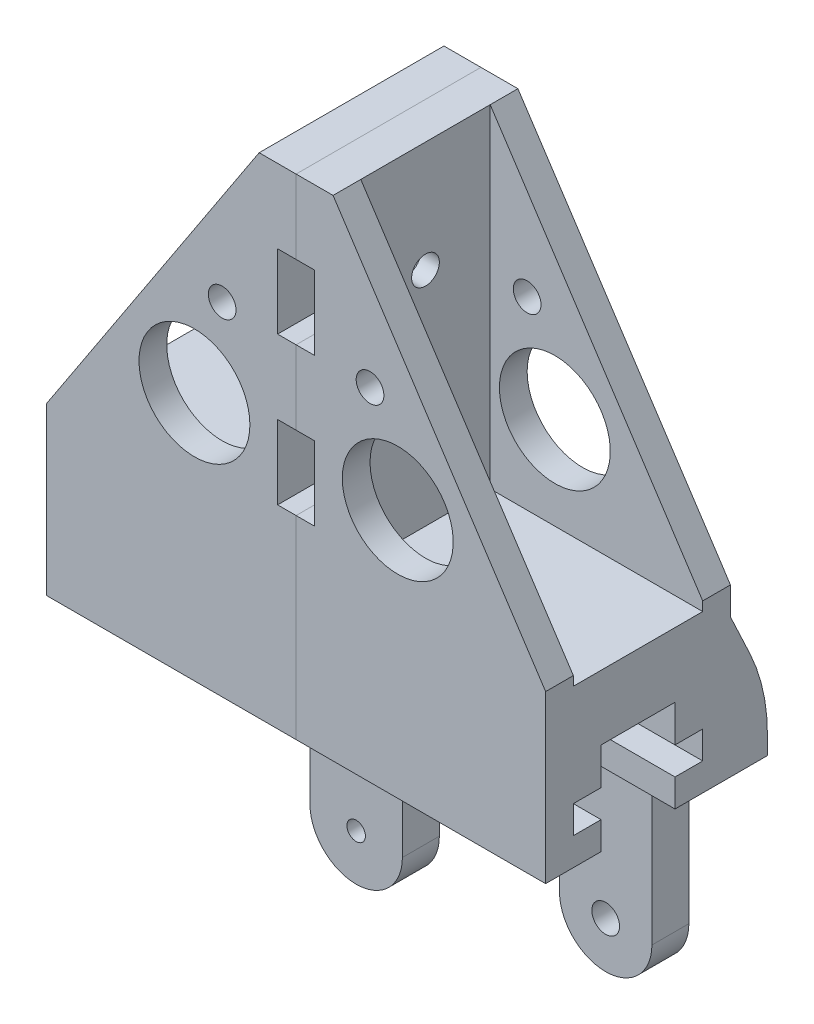
SolidWorks part; units mm, degrees
material "普通碳钢"
ref_plane "前视" through (0, 0, 0) normal (0, 0, 1) x (1, 0, 0)
ref_plane "上视" through (0, 0, 0) normal (0, 1, 0) x (1, 0, 0)
ref_plane "右视" through (0, 0, 0) normal (1, 0, 0) x (0, 0, -1)
sketch "草图1" plane through (0, 0, 0) normal (0, 0, 1) x (1, 0, 0)
  line L0 (0, 0) -> (2, 0)
  line L1 (2, 0) -> (25, -35)
  line L2 (25, -35) -> (25, -38)
  line L3 (25, -38) -> (0, -38)
  line L4 (0, -38) -> (0, 0)
  dimension "D1" = 38
  dimension "25" = 25
  dimension "D2" = 3
  dimension "D3" = 2
extrude "凸台-拉伸1" add sketch "草图1" along normal mid plane 20
shell "抽壳1" thickness 3 removed face at (13.5, -17.5, 0)
sketch "草图2" plane through (0, 0, 0) normal (0, 0, 1) x (1, 0, 0)
  line L0 (2, 0) -> (2, -36)
  line L1 (2, 0) -> (0, 0) construction
  line L2 (2, -36) -> (25, -36)
  line L3 (25, -38) -> (25, -35) construction
  line L4 (25, -36) -> (25, -35)
  line L5 (25, -35) -> (22, -30.4348)
  line L6 (22, -30.4348) -> (22, -35)
  line L7 (22, -35) -> (22, -30.4348) construction
  line L8 (3, -35) -> (22, -35) construction
  line L9 (22, -35) -> (3, -35)
  line L10 (3, -35) -> (3, -3)
  line L11 (3, -3) -> (3.9714, -3)
  line L12 (3.9714, -3) -> (2, 0)
  line L13 (0, -38) -> (25, -38) construction
  dimension "D1" = 2
extrude "切除-拉伸1" cut sketch "草图2" against normal mid plane 14
sketch "草图3" plane through (0, 0, 0) normal (0, 0, 1) x (1, 0, 0)
  line L1 (0, 0) -> (0, -38) construction
  line L2 (0, 0) -> (-2, 0)
  line L3 (0, 0) -> (0, -8)
  line L4 (0, -8) -> (-2, -8)
  line L5 (-2, 0) -> (-2, -8)
  line L6 (0, -16) -> (-2, -16)
  line L7 (0, -16) -> (0, -24)
  line L8 (0, -24) -> (-2, -24)
  line L9 (-2, -16) -> (-2, -24)
  line L10 (0, -38) -> (25, -38) construction
  line L11 (0, -32) -> (-2, -32)
  line L12 (0, -32) -> (0, -38)
  line L13 (0, -38) -> (-2, -38)
  line L14 (-2, -32) -> (-2, -38)
  dimension "D1" = 2
  dimension "D2" = 6
  dimension "D3" = 8
  dimension "D4" = 8
  dimension "D5" = 8
extrude "凸台-拉伸2" add sketch "草图3" along normal mid plane 20
sketch "草图4" plane through (0, 0, -10) normal (0, 0, -1) x (-1, 0, 0)
  line L0 (2, -38) -> (-25, -38) construction
  line L1 (0, -24) -> (0, -32) construction
  line L2 (0, -8) -> (0, -16) construction
  circle A0 centre (-9, -26) radius 6
  circle A1 centre (-6, -16) radius 1.5
  dimension "D1" = 12
  dimension "D2" = 3
  dimension "D3" = 12
  dimension "D4" = 9
  dimension "D5" = 22
  dimension "D6" = 6
extrude "切除-拉伸2" cut sketch "草图4" against normal blind 20
sketch "草图5" plane through (0, 0, 0) normal (-1, 0, 0) x (0, 0, 1)
  line L0 (0, 0) -> (0, -38) construction
  line L1 (10, -38) -> (-10, -38) construction
  line L2 (-10, -12) -> (10, -12) construction
  line L3 (-10, -8) -> (-10, -16) construction
  line L4 (10, -8) -> (10, -16) construction
  line L5 (-10, -28) -> (10, -28) construction
  line L6 (-10, -24) -> (-10, -32) construction
  line L7 (10, -24) -> (10, -32) construction
  circle A0 centre (0, -12) radius 1.5
  circle A1 centre (0, -28) radius 1.5
  dimension "D1" = 3
extrude "切除-拉伸3" cut sketch "草图5" against normal blind 20
sketch "草图6" plane through (25, 0, 0) normal (1, 0, 0) x (0, 0, -1)
  line L0 (-10, -38) -> (-10, -53)
  line L1 (-10, -38) -> (10, -38)
  line L2 (10, -38) -> (12.1176, -42.5294)
  line L3 (14, -51) -> (14, -53)
  line L4 (14, -53) -> (4, -53)
  line L7 (4, -50) -> (4, -53)
  line L8 (7, -50) -> (4, -50)
  line L9 (7, -47) -> (7, -50)
  line L10 (4, -47) -> (7, -47)
  line L11 (4, -43) -> (4, -47)
  line L12 (-4, -43) -> (4, -43)
  line L13 (-4, -43) -> (-4, -47)
  line L14 (-4, -47) -> (-7, -47)
  line L15 (-7, -47) -> (-7, -50)
  line L16 (-7, -50) -> (-4, -50)
  line L17 (-4, -50) -> (-4, -53)
  line L18 (-4, -53) -> (-10, -53)
  line L22 (0, -38) -> (0, -52.3559) construction
  arc A0 (14, -51) -> (12.1176, -42.5294) centre (-6, -51) ccw
  dimension "D8" = 20
  dimension "D1" = 15
  dimension "D2" = 3
  dimension "D3" = 3
  dimension "D4" = 4
  dimension "D5" = 6
  dimension "D6" = 3
  dimension "D7" = 6
  dimension "D9" = 10
  dimension "D10" = 2
extrude "凸台-拉伸3" add sketch "草图6" against normal up to surface (27 mm away) up to face at (-2, -35, 0)
sketch "草图7" plane through (0, 0, -14) normal (0, 0, -1) x (-1, 0, 0)
  line L0 (-11.5, -53) -> (-11.5, -73) construction
  line L1 (2, -53) -> (-25, -53) construction
  line L2 (-6.5, -53) -> (-6.5, -73)
  line L3 (-16.5, -53) -> (-16.5, -73)
  line L4 (-16.5, -53) -> (-6.5, -53)
  circle A0 centre (-11.5, -73) radius 1.5
  arc A1 (-16.5, -73) -> (-6.5, -73) centre (-11.5, -73) ccw
  point P4 (-11.5, -53)
  dimension "D2" = 25
  dimension "D3" = 3
  dimension "D1" = 10
extrude "凸台-拉伸4" add sketch "草图7" against normal blind 4
mirror "镜向1" about plane through (-2, -32, 10) normal (1, 0, 0) of bodies 110
sketch "草图8" plane through (0, 0, -14) normal (0, 0, -1) x (-1, 0, 0)
  line L0 (10.5, -73) -> (10.5, -78.3)
  line L2 (20.5, -78.3) -> (20.5, -73)
  arc A0 (10.5, -78.3) -> (20.5, -78.3) centre (15.5, -78.3) ccw
  arc A1 (10.5, -73) -> (20.5, -73) centre (15.5, -73) ccw
extrude "凸台-拉伸5" add sketch "草图8" against normal blind 4
sketch "草图9" plane through (0, 0, -14) normal (0, 0, -1) x (-1, 0, 0)
  circle A0 centre (15.5, -73) radius 1.5
extrude "凸台-拉伸6" add sketch "草图9" against normal blind 4
sketch "草图10" plane through (0, 0, -14) normal (0, 0, -1) x (-1, 0, 0)
  circle A0 centre (15.5, -78.3) radius 1
extrude "切除-拉伸4" cut sketch "草图10" against normal blind 4
